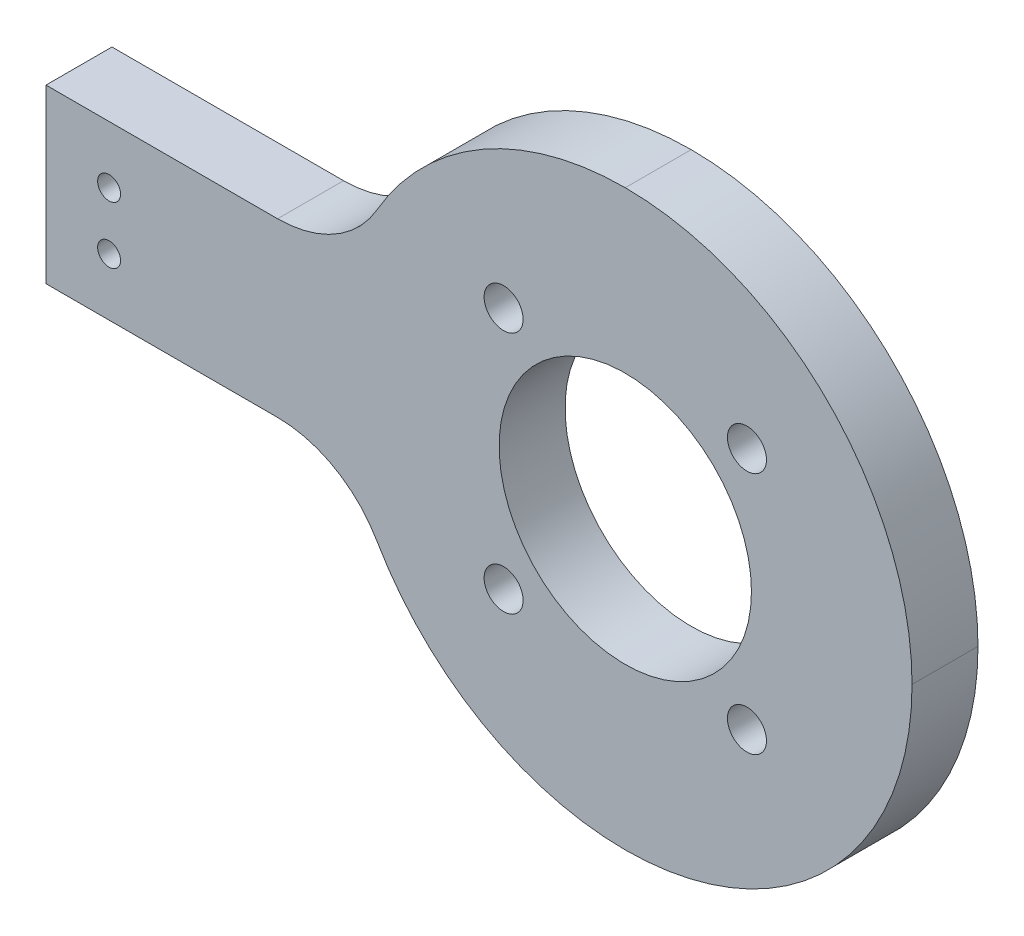
SolidWorks part; units mm, degrees
ref_plane "Front Plane" through (0, 0, 0) normal (0, 0, 1) x (1, 0, 0)
ref_plane "Top Plane" through (0, 0, 0) normal (0, 1, 0) x (1, 0, 0)
ref_plane "Right Plane" through (0, 0, 0) normal (1, 0, 0) x (0, 0, -1)
sketch "Sketch2" plane through (0, 0, 0) normal (0, 1, 0) x (1, 0, 0)
  line L0 (0, 0) -> (-100, 0)
  line L4 (-100, 5.75) -> (0, 5.75)
  line L5 (0, 5.75) -> (0, 0)
  line L6 (-100, 0) -> (-100, 5.75)
  point P6 (0, 2.875)
  point P9 (-68, 0)
  dimension "D1" = 5.75
  dimension "D2" = 100
extrude "Boss-Extrude1" add sketch "Sketch2" along normal blind 50
sketch "Sketch4" plane through (0, 0, 0) normal (0, 0, 1) x (1, 0, 0)
  line L0 (-25, 50) -> (-25, 25) construction
  line L1 (-100, 50) -> (0, 50) construction
  line L2 (-25, 25) -> (0, 25) construction
  line L3 (0, 50) -> (0, 0) construction
  circle A0 centre (-25, 25) radius 11
  dimension "D1" = 22
extrude "Cut-Extrude1" cut sketch "Sketch4" against normal through all
hole_wizard "M3 Clearance Hole2" positions "Sketch5" profile "Sketch6" hole size "M3" standard "ANSI Metric" end condition through all
sketch "Sketch5" plane through (0, 0, 0) normal (0, 0, 1) x (1, 0, 0)
  line L0 (-35.6066, 35.6066) -> (-14.3934, 14.3934) construction
  line L3 (-35.6066, 14.3934) -> (-14.3934, 35.6066) construction
  circle A0 centre (-25, 25) radius 15 construction
  point P5 (-35.6066, 35.6066)
  point P7 (-14.3934, 35.6066)
  point P9 (-14.3934, 14.3934)
  point P11 (-35.6066, 14.3934)
  dimension "D1" = 30
  dimension "D2" = 90
sketch "Sketch6" plane through (-35.6066, 14.3934, 0) normal (1, 0, 0) x (0, -1, 0)
  line L0 (0, 0) -> (0, 5.75)
  line L1 (0, 5.75) -> (1.7, 5.75)
  line L2 (1.7, 5.75) -> (1.7, 0)
  line L5 (1.7, 0) -> (0, 0)
  line L11 (0, -6.35) -> (0, 107.95) construction
  dimension "Thru Hole Dia." = 3.4
  dimension "Thru Hole Depth" = 5.75
sketch "Sketch9" plane through (0, 0, 0) normal (0, 0, 1) x (1, 0, 0)
  line L0 (-25, 50) -> (-100, 50)
  line L3 (-100, 32.5) -> (-48.8485, 32.5)
  line L4 (-25, 25) -> (-100, 25) construction
  line L5 (-100, 50) -> (-100, 0) construction
  line L6 (-100, 50) -> (-100, 32.5)
  line L7 (-100, 50) -> (0, 50) construction
  line L8 (-25, 0) -> (-100, 0)
  line L9 (-100, 17.5) -> (-48.8485, 17.5)
  line L10 (-100, 0) -> (-100, 17.5)
  arc A0 (-25, 50) -> (-48.8485, 32.5) centre (-25, 25) ccw
  arc A1 (-25, 0) -> (-48.8485, 17.5) centre (-25, 25) cw
  dimension "D1" = 7.5
extrude "Cut-Extrude3" cut sketch "Sketch9" against normal up to surface (5.75 mm away) up to face at (-33.9066, 35.6066, -5.75)
fillet "Fillet1" radius 25 2 edges at (0, 0, -2.875) (0, 50, -2.875)
fillet "Fillet2" radius 10 2 edges at (-48.8485, 32.5, -2.875) (-48.8485, 17.5, -2.875)
hole_wizard "M3 Clearance Hole3" positions "Sketch10" profile "Sketch11" hole size "M3" standard "ANSI Metric" end condition through all
sketch "Sketch10" plane through (0, 0, 0) normal (0, 0, 1) x (1, 0, 0)
  line L0 (-25, 25) -> (-100, 25) construction
  line L1 (-100, 32.5) -> (-100, 17.5) construction
  point P0 (-94, 28.5)
  point P2 (-94, 21.5)
  dimension "D1" = 7
  dimension "D2" = 6
sketch "Sketch11" plane through (-94, 28.5, 0) normal (1, 0, 0) x (0, -1, 0)
  line L0 (0, 0) -> (0, 5.75)
  line L1 (0, 5.75) -> (1.7, 5.75)
  line L2 (1.7, 5.75) -> (1.7, 0)
  line L5 (1.7, 0) -> (0, 0)
  line L11 (0, -6.35) -> (0, 107.95) construction
  dimension "Thru Hole Dia." = 3.4
  dimension "Thru Hole Depth" = 5.75
sketch "Sketch12" plane through (0, 0, 0) normal (0, 0, 1) x (1, 0, 0)
  line L0 (-25, 25) -> (-100, 25) construction
  line L1 (-100, 32.5) -> (-100, 17.5) construction
  line L2 (-55.3109, 17.5) -> (-100, 17.5) construction
  line L3 (-100, 32.5) -> (-75.5, 32.5)
  line L4 (-100, 32.5) -> (-100, 17.5)
  line L5 (-100, 17.5) -> (-75.5, 17.5)
  line L6 (-75.5, 32.5) -> (-75.5, 17.5)
  circle A0 centre (-70, 27.5) radius 1
  circle A1 centre (-70, 22.5) radius 1
  dimension "D1" = 2
  dimension "D2" = 5
  dimension "D3" = 30
  dimension "D4" = 5.5
extrude "Cut-Extrude4" cut sketch "Sketch12" against normal up to surface (5.75 mm away) up to face at (-92.3, 28.5, -5.75)
